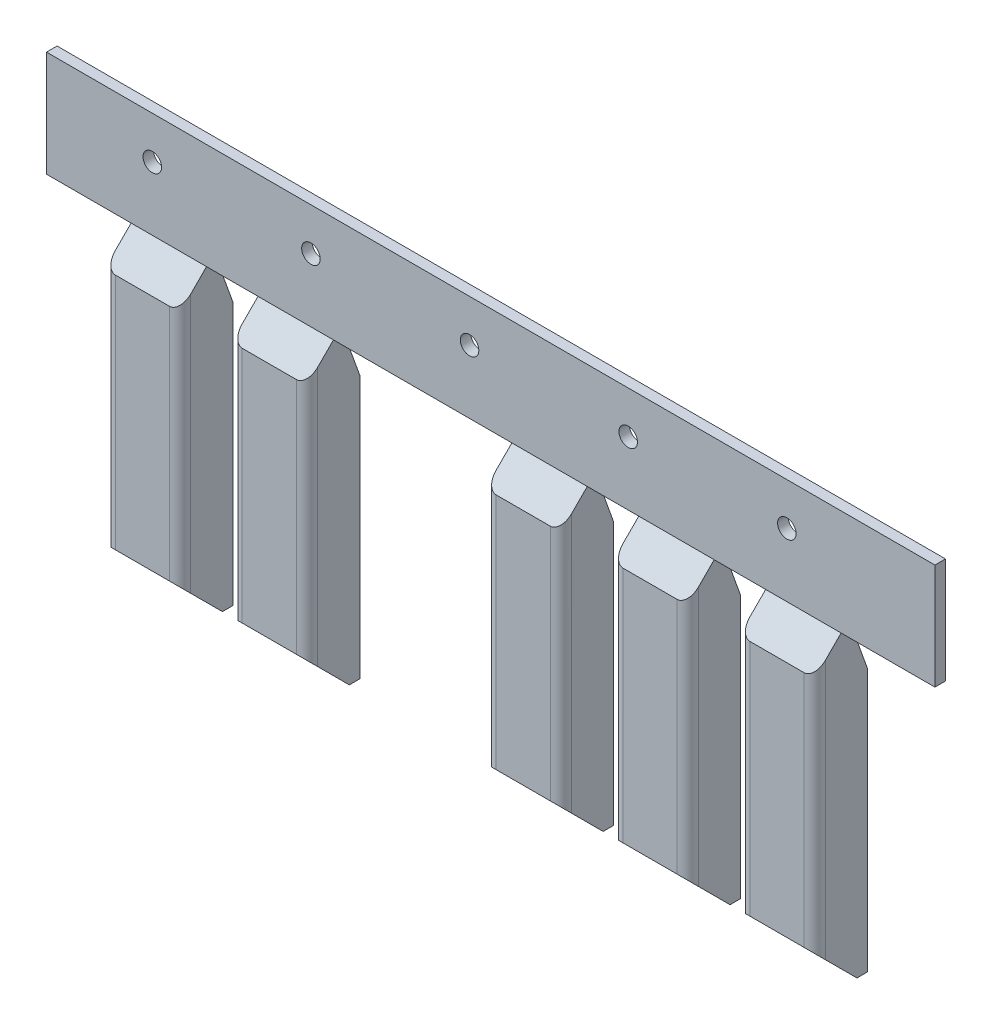
SolidWorks part; units mm, degrees
ref_plane "Front Plane" through (0, 0, 0) normal (0, 0, 1) x (1, 0, 0)
ref_plane "Top Plane" through (0, 0, 0) normal (0, 1, 0) x (1, 0, 0)
ref_plane "Right Plane" through (0, 0, 0) normal (1, 0, 0) x (0, 0, -1)
sketch "Sketch1" plane through (0, 0, 0) normal (0, 0, 1) x (1, 0, 0)
  line L1 (-84, 60) -> (84, 60)
  line L2 (-84, 60) -> (-84, -60)
  line L3 (-84, -60) -> (84, -60)
  line L4 (84, 60) -> (84, -60)
  line L5 (-84, 60) -> (84, -60) construction
  line L6 (-84, -60) -> (84, 60) construction
  point P0 (0, 0)
  dimension "D1" = 120
  dimension "D2" = 168
extrude "Boss-Extrude1" add sketch "Sketch1" along normal blind 10
sketch "Sketch2" plane through (0, 0, 10) normal (0, 0, 1) x (1, 0, 0)
  line L0 (84, 60) -> (-84, 60) construction
  line L1 (-68, 40) -> (-53.7367, 40) construction
  line L2 (-68, 40) -> (-68, -18)
  line L3 (-68, -18) -> (-53.7367, -18)
  line L4 (-53.7367, 40) -> (-53.7367, -18)
  line L5 (-84, 60) -> (-84, -60) construction
  line L6 (-29.7367, 40) -> (-29.7367, -18)
  line L7 (-44, -18) -> (-29.7367, -18)
  line L8 (-44, 40) -> (-44, -18)
  line L9 (-44, 40) -> (-29.7367, 40) construction
  line L14 (18.2633, 40) -> (18.2633, -18)
  line L15 (4, -18) -> (18.2633, -18)
  line L16 (4, 40) -> (4, -18)
  line L17 (4, 40) -> (18.2633, 40) construction
  line L18 (42.2633, 40) -> (42.2633, -18)
  line L19 (28, -18) -> (42.2633, -18)
  line L20 (28, 40) -> (28, -18)
  line L21 (28, 40) -> (42.2633, 40) construction
  line L22 (66.2633, 40) -> (66.2633, -18)
  line L23 (52, -18) -> (66.2633, -18)
  line L24 (52, 40) -> (52, -18)
  line L25 (52, 40) -> (66.2633, 40) construction
  line L26 (-68, 40) -> (-84, 40)
  line L27 (-84, 40) -> (-84, -60)
  line L28 (-84, -60) -> (84, -60)
  line L29 (84, -60) -> (84, 40)
  line L30 (84, -60) -> (84, 60) construction
  line L31 (84, 40) -> (66.2633, 40)
  line L32 (52, 40) -> (42.2633, 40)
  line L33 (28, 40) -> (18.2633, 40)
  line L34 (-29.7367, 40) -> (4, 40)
  line L35 (-53.7367, 40) -> (-44, 40)
  line L37 (-5.7367, 40) -> (-5.7367, -18) construction
  line L38 (-20, -18) -> (-5.7367, -18) construction
  line L39 (-20, 40) -> (-20, -18) construction
  line L40 (-20, 40) -> (-5.7367, 40) construction
  dimension "D1" = 20
  dimension "D2" = 16
  dimension "D3" = 58
  dimension "D4" = 6
extrude "Cut-Extrude1" cut sketch "Sketch2" against normal through all
chamfer "Chamfer1" distance 8 angle 45 5 edges at (59.1316, -18, 10) (35.1316, -18, 10) (11.1316, -18, 10) (-36.8684, -18, 10) (-60.8684, -18, 10)
fillet "Fillet1" radius 2 10 edges at (66.2633, 15, 10) (52, 15, 10) (42.2633, 15, 10) (28, 15, 10) (18.2633, 15, 10) (4, 15, 10) (-29.7367, 15, 10) (-44, 15, 10) (-53.7367, 15, 10) (-68, 15, 10)
sketch "Sketch3" plane through (0, 0, 10) normal (0, 0, 1) x (1, 0, 0)
  line L1 (-84, 60) -> (84, 60)
  line L2 (-84, 60) -> (-84, 40)
  line L3 (-84, 40) -> (84, 40)
  line L4 (84, 60) -> (84, 40)
extrude "Cut-Extrude2" cut sketch "Sketch3" against normal blind 5
sketch "Sketch4" plane through (0, 0, 0) normal (0, 0, -1) x (-1, 0, 0)
  line L1 (-84, 60) -> (84, 60)
  line L2 (-84, 60) -> (-84, 40)
  line L3 (-84, 40) -> (84, 40)
  line L4 (84, 60) -> (84, 40)
extrude "Cut-Extrude3" cut sketch "Sketch4" against normal blind 3
chamfer "Chamfer2" distance 5 angle 45 5 edges at (59.1316, 40, 10) (35.1316, 40, 10) (11.1316, 40, 10) (-36.8684, 40, 10) (-60.8684, 40, 10) tangent propagation no
shell "Shell1" thickness 2 removed face at (59.1316, 11, 0) removed face at (35.1316, 11, 0) removed face at (11.1316, 11, 0) removed face at (-36.8684, 11, 0) removed face at (-60.8684, 11, 0) removed face at (-84, 50, 4)
sketch "Sketch5" plane through (-68, 0, 0) normal (-1, 0, 0) x (0, 0, 1)
  line L0 (3, 40) -> (0, 31.6731)
  line L1 (0, -18) -> (0, 40) construction
  line L2 (0, 31.6731) -> (0, 40)
  line L3 (0, 40) -> (3, 40)
extrude "Cut-Extrude4" cut sketch "Sketch5" against normal through all
sketch "Sketch6" plane through (0, 0, 5) normal (0, 0, 1) x (1, 0, 0)
  line L0 (84, 60) -> (-84, 60) construction
  line L1 (-84, 60) -> (-84, 40) construction
  circle A0 centre (-64, 52) radius 1.75
  circle A1 centre (-34, 52) radius 1.75
  circle A2 centre (-4, 52) radius 1.75
  circle A3 centre (26, 52) radius 1.75
  circle A4 centre (56, 52) radius 1.75
  dimension "D3" = 3.5
  dimension "D1" = 8
  dimension "D2" = 20
  dimension "D4" = 5
extrude "Cut-Extrude5" cut sketch "Sketch6" against normal through all
